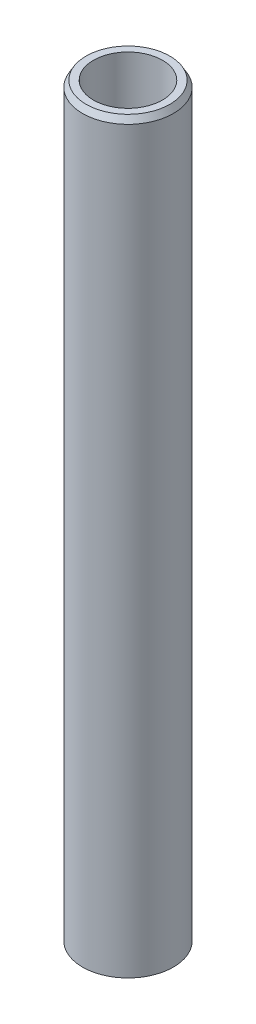
SolidWorks part; units mm, degrees
ref_plane "Front Plane" through (0, 0, 0) normal (0, 0, 1) x (1, 0, 0)
ref_plane "Top Plane" through (0, 0, 0) normal (0, 1, 0) x (1, 0, 0)
ref_plane "Right Plane" through (0, 0, 0) normal (1, 0, 0) x (0, 0, -1)
sketch "Sketch1" plane through (0, 0, 0) normal (0, 1, 0) x (1, 0, 0)
  circle A0 centre (0, 0) radius 35
  dimension "SHAFT_OD" = 70
extrude "Boss-Extrude1" add sketch "Sketch1" along normal blind 577.3247
sketch "Sketch2" plane through (0, 0, 0) normal (0, 1, 0) x (1, 0, 0)
  circle A0 centre (0, 0) radius 26.6122
  dimension "BORE_D" = 53.2243
extrude "Cut-Extrude1" cut sketch "Sketch2" along normal through all
chamfer "Chamfer1" distance 4.7552 angle 30 2 edges at (0, 577.3247, 35) (0, 0, 35) first distance on face at (0, 577.3247, 35) first distance on face at (0, 0, 26.6122)
